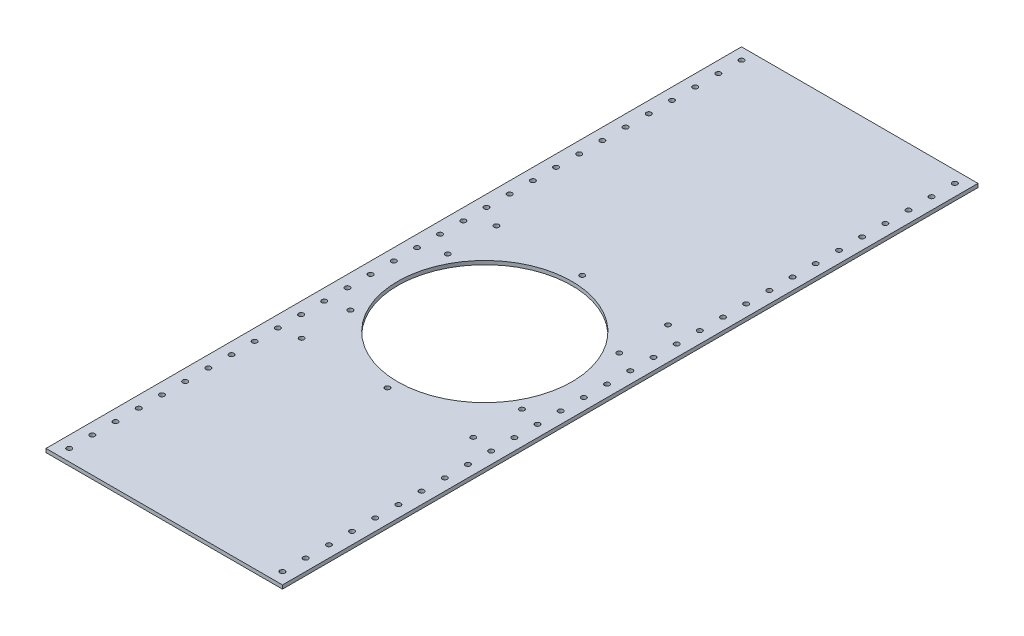
SolidWorks part; units mm, degrees
ref_plane "Front Plane" through (0, 0, 0) normal (0, 0, 1) x (1, 0, 0)
ref_plane "Top Plane" through (0, 0, 0) normal (0, 1, 0) x (1, 0, 0)
ref_plane "Right Plane" through (0, 0, 0) normal (1, 0, 0) x (0, 0, -1)
sketch "Sketch1" plane through (0, 0, 0) normal (0, 1, 0) x (1, 0, 0)
  line L0 (0, 250) -> (0, -350) construction
  line L1 (-102, -350) -> (102, -350)
  line L2 (-102, -350) -> (-102, 250)
  line L3 (-102, 250) -> (102, 250)
  line L4 (102, -350) -> (102, 250)
  line L5 (-102, -350) -> (102, 250) construction
  line L6 (-102, 250) -> (102, -350) construction
  line L7 (-102, -73.451) -> (102, -73.451) construction
  line L8 (92, 250) -> (92, -350) construction
  line L9 (-92, 250) -> (-92, -350) construction
  line L11 (-80, -163.451) -> (80, -163.451) construction
  line L12 (-80, -163.451) -> (-80, 16.549) construction
  line L13 (-80, 16.549) -> (80, 16.549) construction
  line L14 (80, -163.451) -> (80, 16.549) construction
  line L15 (-80, -163.451) -> (80, 16.549) construction
  line L16 (-80, 16.549) -> (80, -163.451) construction
  circle A232 centre (92, 240) radius 2.15
  circle A233 centre (92, 220) radius 2.15
  circle A234 centre (92, 200) radius 2.15
  circle A235 centre (92, 180) radius 2.15
  circle A236 centre (92, 160) radius 2.15
  circle A237 centre (92, 140) radius 2.15
  circle A238 centre (92, 120) radius 2.15
  circle A239 centre (92, 100) radius 2.15
  circle A240 centre (92, 80) radius 2.15
  circle A241 centre (92, 60) radius 2.15
  circle A242 centre (92, 40) radius 2.15
  circle A243 centre (92, 20) radius 2.15
  circle A244 centre (92, 0) radius 2.15
  circle A245 centre (92, -20) radius 2.15
  circle A246 centre (92, -40) radius 2.15
  circle A247 centre (92, -60) radius 2.15
  circle A248 centre (92, -80) radius 2.15
  circle A249 centre (92, -100) radius 2.15
  circle A250 centre (92, -120) radius 2.15
  circle A251 centre (92, -140) radius 2.15
  circle A252 centre (92, -160) radius 2.15
  circle A253 centre (92, -180) radius 2.15
  circle A254 centre (92, -200) radius 2.15
  circle A255 centre (92, -220) radius 2.15
  circle A256 centre (92, -240) radius 2.15
  circle A257 centre (92, -260) radius 2.15
  circle A258 centre (92, -280) radius 2.15
  circle A259 centre (92, -300) radius 2.15
  circle A260 centre (92, -320) radius 2.15
  circle A261 centre (92, -340) radius 2.15
  circle A262 centre (-92, -340) radius 2.15
  circle A263 centre (-92, -320) radius 2.15
  circle A264 centre (-92, -300) radius 2.15
  circle A265 centre (-92, -280) radius 2.15
  circle A266 centre (-92, -260) radius 2.15
  circle A267 centre (-92, -240) radius 2.15
  circle A268 centre (-92, -220) radius 2.15
  circle A269 centre (-92, -200) radius 2.15
  circle A270 centre (-92, -180) radius 2.15
  circle A271 centre (-92, -160) radius 2.15
  circle A272 centre (-92, -140) radius 2.15
  circle A273 centre (-92, -120) radius 2.15
  circle A274 centre (-92, -100) radius 2.15
  circle A275 centre (-92, -80) radius 2.15
  circle A276 centre (-92, -60) radius 2.15
  circle A277 centre (-92, -40) radius 2.15
  circle A278 centre (-92, -20) radius 2.15
  circle A279 centre (-92, 0) radius 2.15
  circle A280 centre (-92, 20) radius 2.15
  circle A281 centre (-92, 40) radius 2.15
  circle A282 centre (-92, 60) radius 2.15
  circle A283 centre (-92, 80) radius 2.15
  circle A284 centre (-92, 100) radius 2.15
  circle A285 centre (-92, 120) radius 2.15
  circle A286 centre (-92, 140) radius 2.15
  circle A287 centre (-92, 160) radius 2.15
  circle A288 centre (-92, 180) radius 2.15
  circle A289 centre (-92, 200) radius 2.15
  circle A290 centre (-92, 220) radius 2.15
  circle A291 centre (-92, 240) radius 2.15
  circle A292 centre (0, -73.451) radius 62.5 construction
  circle A293 centre (-74, -157.451) radius 2.125
  circle A294 centre (-74, -115.451) radius 2.125
  circle A296 centre (0, -157.451) radius 2.125
  circle A297 centre (74, -157.451) radius 2.125
  circle A298 centre (74, -115.451) radius 2.125
  circle A299 centre (74, -31.451) radius 2.125
  circle A300 centre (74, 10.549) radius 2.125
  circle A301 centre (0, 10.549) radius 2.125
  circle A302 centre (-74, 10.549) radius 2.125
  circle A303 centre (-74, -31.451) radius 2.125
  circle A310 centre (0, -73.451) radius 75.125
  dimension "D3" = 10
  dimension "D8" = 180
  dimension "D9" = 4.25
  dimension "D11" = 6
  dimension "D16" = 150.25
  dimension "D17" = 4.25
  dimension "D4" = 4.3
  dimension "D6" = 125
  dimension "D13" = 4.25
  dimension "D2" = 600
  dimension "D5" = 10
  dimension "D7" = 160
  dimension "D12" = 42
  dimension "D15" = 276.549
  dimension "D18" = 6
  dimension "D24" = 204
  dimension "D10" = 6
  dimension "D14" = 0
extrude "Boss-Extrude1" add sketch "Sketch1" along normal blind 3.175
equation "\"m3\"=3.2"
